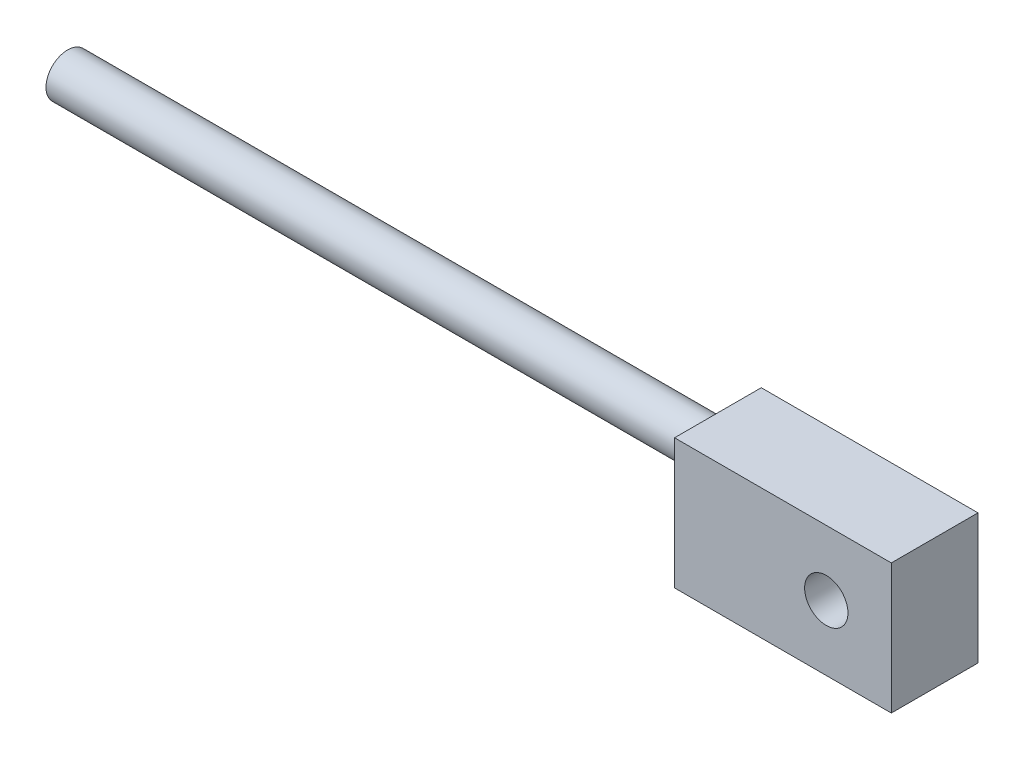
SolidWorks part; units mm, degrees
ref_plane "Спереди" through (0, 0, 0) normal (0, 0, 1) x (1, 0, 0)
ref_plane "Сверху" through (0, 0, 0) normal (0, 1, 0) x (1, 0, 0)
ref_plane "Справа" through (0, 0, 0) normal (1, 0, 0) x (0, 0, -1)
sketch "Эскиз1" plane through (0, 0, 0) normal (0, 0, 1) x (1, 0, 0)
  line L0 (0, 0) -> (30, 0) construction
  line L1 (30, 30) -> (-70, 30)
  line L2 (30, 30) -> (30, -30)
  line L3 (30, -30) -> (-70, -30)
  line L4 (-70, 30) -> (-70, -30)
  circle A0 centre (0, 0) radius 10
  dimension "D1" = 20
  dimension "D2" = 60
  dimension "D3" = 30
  dimension "D4" = 100
extrude "Бобышка-Вытянуть1" add sketch "Эскиз1" along normal blind 20 and the other way blind 20
sketch "Эскиз2" plane through (-70, 0, 0) normal (-1, 0, 0) x (0, 0, 1)
  line L0 (0, 0) -> (0, 15) construction
  circle A0 centre (0, 15) radius 10
  dimension "D1" = 20
  dimension "D2" = 15
extrude "Бобышка-Вытянуть2" add sketch "Эскиз2" along normal blind 300
